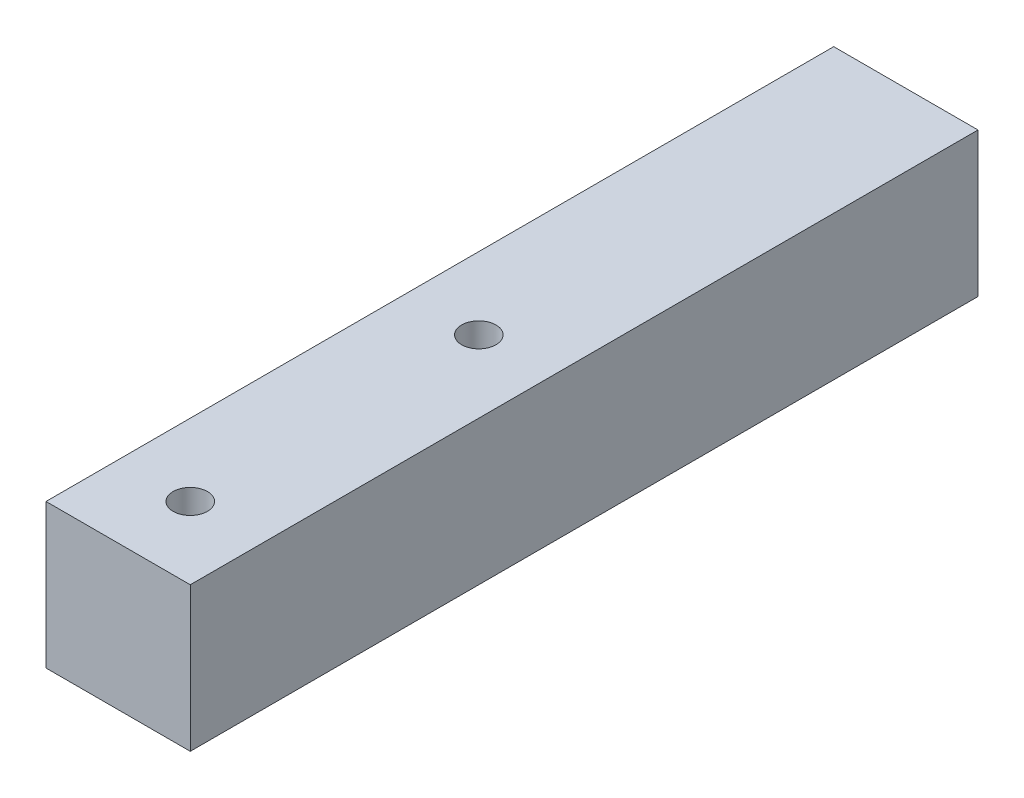
SolidWorks part; units mm, degrees
ref_plane "Front Plane" through (0, 0, 0) normal (0, 0, 1) x (1, 0, 0)
ref_plane "Top Plane" through (0, 0, 0) normal (0, 1, 0) x (1, 0, 0)
ref_plane "Right Plane" through (0, 0, 0) normal (1, 0, 0) x (0, 0, -1)
sketch "Sketch1" plane through (0, 0, 0) normal (0, 0, 1) x (1, 0, 0)
  line L1 (-12.7, -12.7) -> (12.7, -12.7)
  line L2 (-12.7, -12.7) -> (-12.7, 12.7)
  line L3 (-12.7, 12.7) -> (12.7, 12.7)
  line L4 (12.7, -12.7) -> (12.7, 12.7)
  line L5 (-12.7, -12.7) -> (12.7, 12.7) construction
  line L6 (-12.7, 12.7) -> (12.7, -12.7) construction
  point P0 (0, 0)
  dimension "D1" = 25.4
  dimension "D2" = 25.4
extrude "Boss-Extrude1" add sketch "Sketch1" along normal mid plane 138.683
hole_wizard "Ø6.05 (6.05) Diameter Hole1" positions "Sketch3" profile "Sketch2" hole size "Ø6.05" standard "Lanco STD" end condition through all
sketch "Sketch3" plane through (0, -12.7, 0) normal (0, -1, 0) x (-1, 0, 0)
  line L0 (12.7, -69.3415) -> (-12.7, -69.3415) construction
  point P0 (0, -5.8415)
  point P2 (0, -56.6415)
  point P5 (0, -69.3415)
  dimension "D1" = 63.5
  dimension "D2" = 12.7
sketch "Sketch2" plane through (0, -12.7, 5.8415) normal (1, 0, 0) x (0, 0, -1)
  line L0 (0, 0) -> (0, 25.4)
  line L1 (0, 25.4) -> (3.025, 25.4)
  line L2 (3.025, 25.4) -> (3.025, 0)
  line L5 (3.025, 0) -> (0, 0)
  line L11 (0, -6.35) -> (0, 107.95) construction
  dimension "Thru Hole Dia." = 6.05
  dimension "Thru Hole Depth" = 25.4
